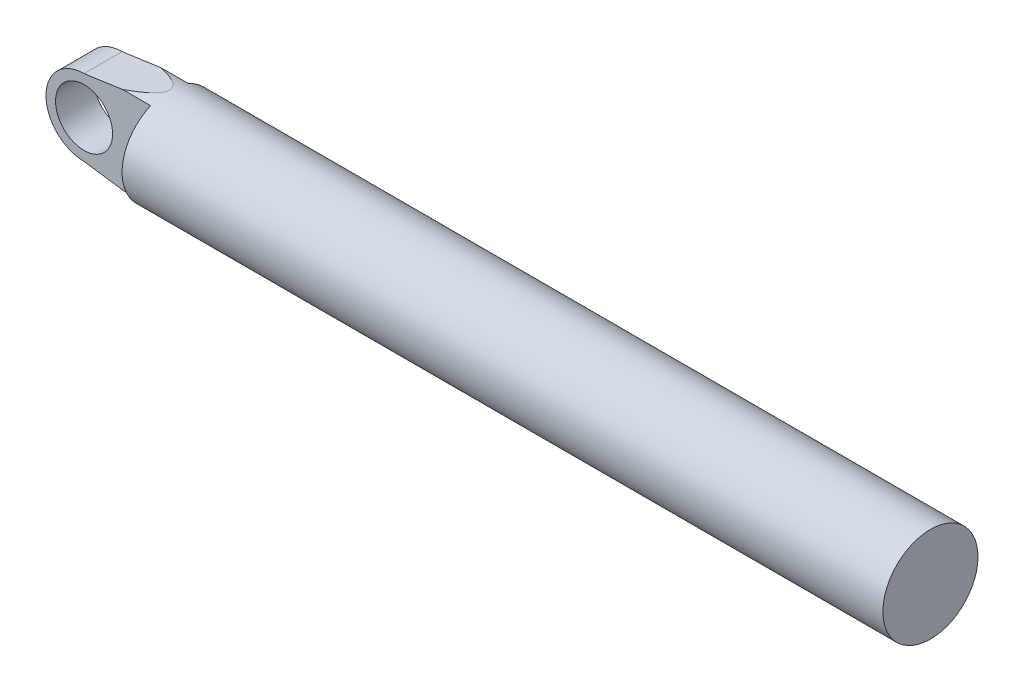
SolidWorks part; units mm, degrees
ref_plane "Front Plane" through (0, 0, 0) normal (0, 0, 1) x (1, 0, 0)
ref_plane "Top Plane" through (0, 0, 0) normal (0, 1, 0) x (1, 0, 0)
ref_plane "Right Plane" through (0, 0, 0) normal (1, 0, 0) x (0, 0, -1)
sketch "Sketch1" plane through (0, 0, 0) normal (1, 0, 0) x (0, 0, -1)
  circle A0 centre (0, 0) radius 25
  dimension "D1" = 50
extrude "Boss-Extrude1" add sketch "Sketch1" along normal blind 400
sketch "Sketch2" plane through (0, 0, 0) normal (0, 0, 1) x (1, 0, 0)
  line L0 (0, 25) -> (0, -25)
  line L1 (0, 25) -> (-35, 20)
  line L2 (-35, -20) -> (0, -25)
  circle A0 centre (-35, 0) radius 15
  arc A1 (-35, 20) -> (-35, -20) centre (-35, 0) ccw
  dimension "D1" = 30
  dimension "D2" = 35
extrude "Boss-Extrude2" add sketch "Sketch2" along normal blind 10 and the other way blind 10
sketch "Sketch3" plane through (0, 0, 0) normal (1, 0, 0) x (0, 0, -1)
  circle A0 centre (0, 0) radius 25
  circle A1 centre (0, 0) radius 32.2413
extrude "Cut-Extrude1" cut sketch "Sketch3" against normal blind 70
